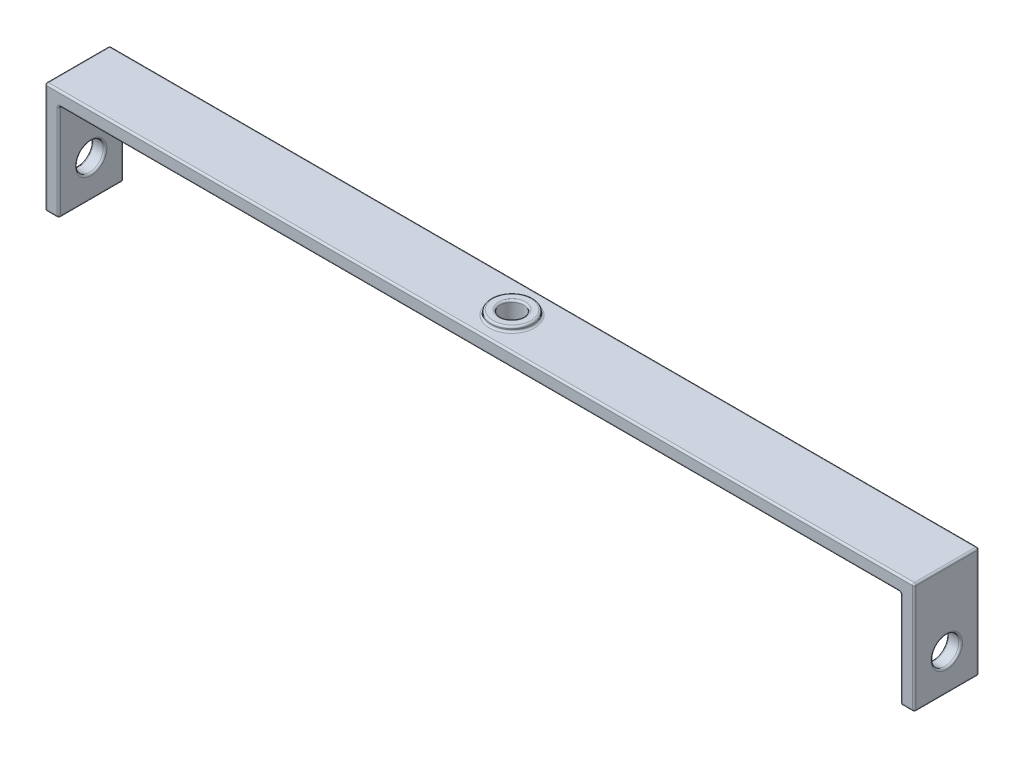
SolidWorks part; units mm, degrees
ref_plane "Front Plane" through (0, 0, 0) normal (0, 0, 1) x (1, 0, 0)
ref_plane "Top Plane" through (0, 0, 0) normal (0, 1, 0) x (1, 0, 0)
ref_plane "Right Plane" through (0, 0, 0) normal (1, 0, 0) x (0, 0, -1)
sketch "Sketch1" plane through (0, 0, 0) normal (0, 0, 1) x (1, 0, 0)
  line L0 (-47, -12) -> (-47, 0)
  line L1 (-47, 0) -> (47, 0)
  line L2 (47, 0) -> (47, -12)
  line L3 (-45.5, -12) -> (-45.5, -1.5)
  line L4 (-45.5, -1.5) -> (45.5, -1.5)
  line L5 (45.5, -1.5) -> (45.5, -12)
  line L6 (-47, -12) -> (-45.5, -12)
  line L7 (45.5, -12) -> (47, -12)
  point P6 (0, 0)
  dimension "D1" = 94
  dimension "D2" = 12
  dimension "D3" = 1.5
extrude "Boss-Extrude1" add sketch "Sketch1" along normal blind 3.5 and the other way blind 3.5
sketch "Sketch2" plane through (0, 0, 0) normal (0, 1, 0) x (1, 0, 0)
  circle A0 centre (0, 0) radius 1.25
  dimension "D1" = 2.5
extrude "Cut-Extrude1" cut sketch "Sketch2" against normal blind 3.5
sketch "Sketch3" plane through (0, 0, 0) normal (0, 1, 0) x (1, 0, 0)
  circle A0 centre (0, 0) radius 1.25 construction
  circle A1 centre (0, 0) radius 1.25
  circle A2 centre (0, 0) radius 2.25
  dimension "D1" = 1
extrude "Boss-Extrude2" add sketch "Sketch3" along normal blind 0.5
sketch "Sketch4" plane through (0, 0, 0) normal (1, 0, 0) x (0, 0, -1)
  line L0 (0, 0.5) -> (0, -8) construction
  line L1 (2.25, 0.5) -> (-2.25, 0.5) construction
  circle A0 centre (0, -8) radius 1.5
  dimension "D2" = 3
  dimension "D1" = 8.5
extrude "Cut-Extrude2" cut sketch "Sketch4" against normal through all both and the other way through all
fillet "Fillet1" radius 0.2 32 edges at (47, -8, -1.5) (-47, -8, -1.5) (-45.5, -8, -1.5) (45.5, -8, 1.5) (-1.25, 0.5, 0) (-2.25, 0, 0) (-2.25, 0.5, 0) (0, -1.5, -1.25) (-46.25, -12, 3.5) (-45.5, -6.75, 3.5) (0, -1.5, 3.5) (45.5, -6.75, 3.5) (46.25, -12, 3.5) (47, -6, 3.5) (-47, -6, 3.5) (-46.25, -12, -3.5) (-45.5, -6.75, -3.5) (0, -1.5, -3.5) (45.5, -6.75, -3.5) (46.25, -12, -3.5) (47, -6, -3.5) (0, 0, -3.5) (-47, -6, -3.5) (-45.5, -12, 0) (-45.5, -1.5, 0) (45.5, -1.5, 0) (45.5, -12, 0) (47, -12, 0) (47, 0, 0) (-47, 0, 0) (-47, -12, 0) (0, 0, 3.5)
